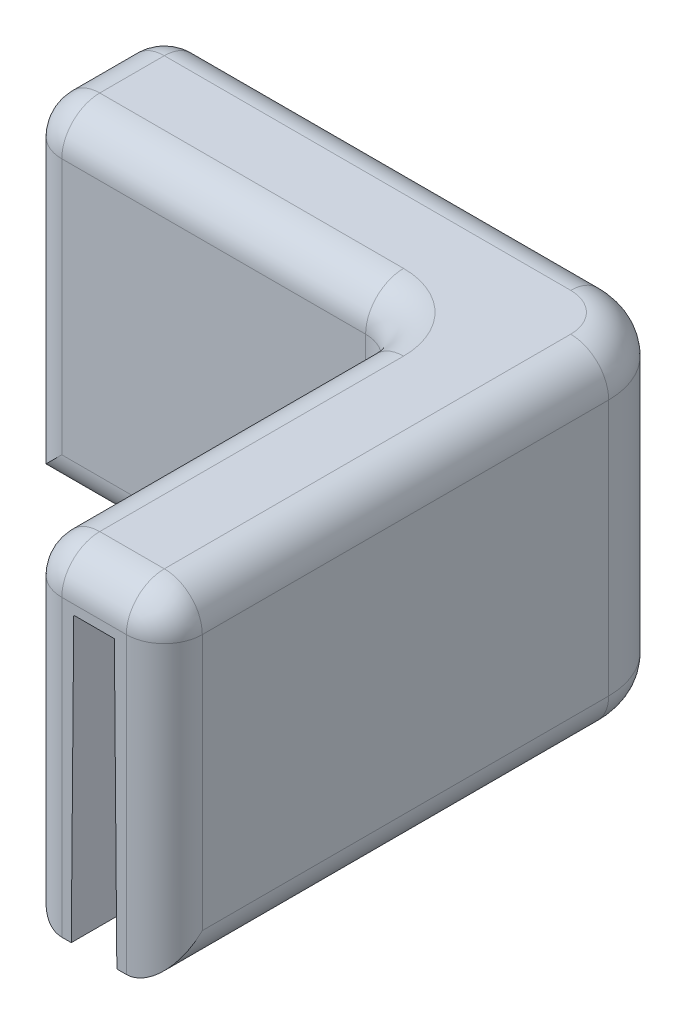
SolidWorks part; units mm, degrees
ref_plane "Front Plane" through (0, 0, 0) normal (0, 0, 1) x (1, 0, 0)
ref_plane "Top Plane" through (0, 0, 0) normal (0, 1, 0) x (1, 0, 0)
ref_plane "Right Plane" through (0, 0, 0) normal (1, 0, 0) x (0, 0, -1)
sketch "Sketch1" plane through (0, 0, 0) normal (0, 1, 0) x (1, 0, 0)
  line L0 (-34.798, 0) -> (0, 0)
  line L1 (0, 0) -> (0, -34.798)
  line L2 (0, -34.798) -> (-9.398, -34.798)
  line L3 (-9.398, -34.798) -> (-9.398, -9.398)
  line L4 (-9.398, -9.398) -> (-34.798, -9.398)
  line L5 (-34.798, -9.398) -> (-34.798, 0)
  line L6 (-34.798, -3.175) -> (-3.175, -3.175) construction
  line L7 (-3.175, -3.175) -> (-3.175, -34.798) construction
  line L8 (-3.175, -34.798) -> (-6.223, -34.798) construction
  line L9 (-6.223, -34.798) -> (-6.223, -6.223) construction
  line L10 (-6.223, -6.223) -> (-34.798, -6.223) construction
  line L11 (-34.798, -6.223) -> (-34.798, -3.175) construction
  point P17 (-34.798, -4.699)
  point P18 (-34.798, -4.699)
  dimension "D1" = 3.048
  dimension "D2" = 25.4
  dimension "D3" = 3.175
extrude "Boss-Extrude1" add sketch "Sketch1" along normal blind 22.225
sketch "Sketch2" plane through (0, 0, 0) normal (0, -1, 0) x (1, 0, 0)
  line L0 (-3.175, 40.346) -> (-6.223, 40.346)
  line L1 (-6.223, 40.346) -> (-6.223, 6.223)
  line L2 (-6.223, 6.223) -> (-37.9118, 6.223)
  line L3 (-37.9118, 6.223) -> (-37.9118, 3.175)
  line L4 (-37.9118, 3.175) -> (-3.175, 3.175)
  line L5 (-3.175, 3.175) -> (-3.175, 40.346)
extrude "Cut-Extrude1" cut sketch "Sketch2" against normal blind 19.05 draft 0.5
fillet "Fillet1" radius 5.08 2 edges at (0, 11.1125, 0) (-6.1399, 9.525, 6.1399)
fillet "Fillet2" radius 2.54 17 edges at (-9.398, 0, 22.098) (0, 0, 19.939) (-1.4879, 0, 1.4879) (0, 22.225, 19.939) (-1.4879, 22.225, 1.4879) (-34.798, 11.1125, 9.398) (-22.098, 22.225, 9.398) (-9.398, 11.1125, 9.398) (-22.098, 0, 9.398) (-19.939, 0, 0) (-34.798, 11.1125, 0) (0, 11.1125, 34.798) (-9.398, 11.1125, 34.798) (-4.699, 22.225, 34.798) (-9.398, 22.225, 22.098) (-34.798, 22.225, 4.699) (-19.939, 22.225, 0)
equation "\"bottomThickness\"= .25in"
equation "\"wallThickness\"= .125in"
equation "\"D1@Sketch1\"=\"wallThickness\"-.005in"
